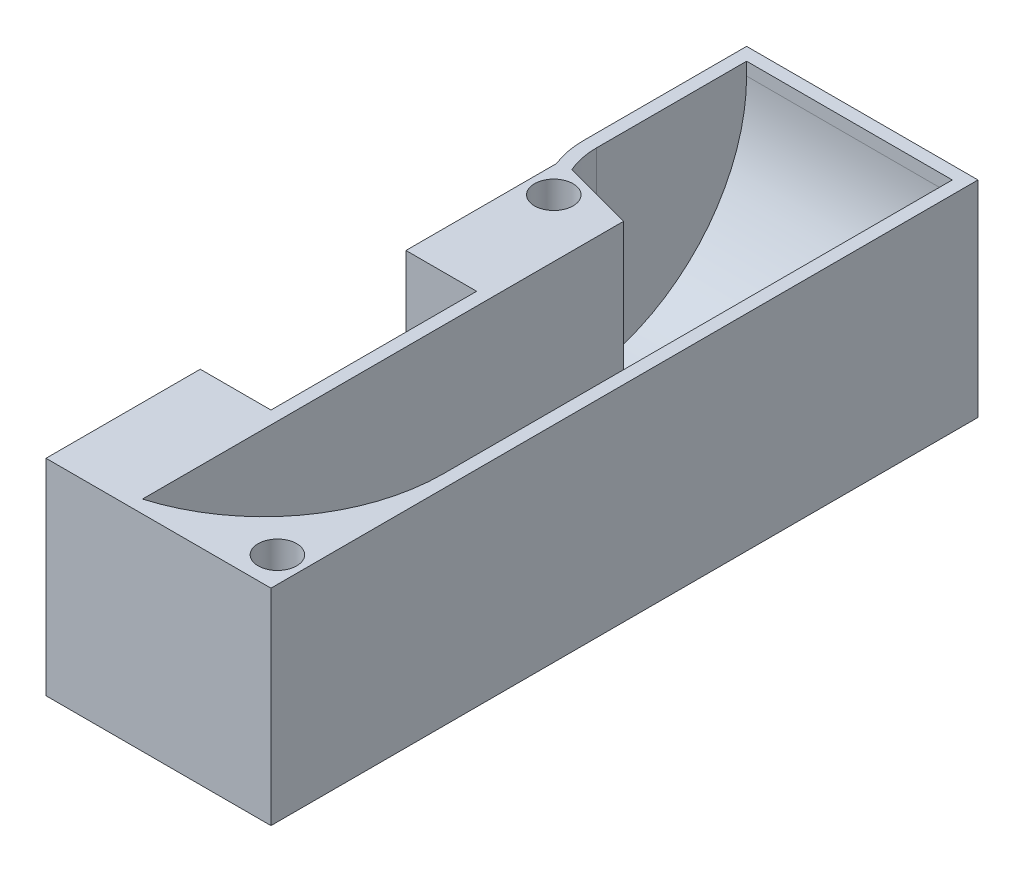
SolidWorks part; units mm, degrees
ref_plane "Front Plane" through (0, 0, 0) normal (0, 0, 1) x (1, 0, 0)
ref_plane "Top Plane" through (0, 0, 0) normal (0, 1, 0) x (1, 0, 0)
ref_plane "Right Plane" through (0, 0, 0) normal (1, 0, 0) x (0, 0, -1)
sketch "Sketch2" plane through (0, 0, 0) normal (0, -1, 0) x (1, 0, 0)
  line L0 (0, 0) -> (13, 0) construction
  line L18 (7.5, -8) -> (7.5, -19.7113)
  line L19 (7, -22.3094) -> (7, -35)
  line L20 (7, -35) -> (25, -35)
  line L21 (25, -35) -> (25, 20)
  line L22 (25, 20) -> (7.5, 20)
  line L23 (7.5, 20) -> (7.5, 8)
  line L24 (7.5, 8) -> (13, 8)
  line L25 (13, 8) -> (13, -8)
  line L26 (13, -8) -> (7.5, -8)
  arc A2 (7.5, -19.7113) -> (7, -22.3094) centre (14, -22.3094) ccw
  point P13 (0, 0)
  dimension "D8" = 7
  dimension "D1" = 13
  dimension "D2" = 16
  dimension "D3" = 5.5
  dimension "D4" = 20
  dimension "D5" = 17.5
  dimension "D6" = 55
  dimension "D7" = 7
  dimension "D9" = 12.6906
extrude "Boss-Extrude2" add sketch "Sketch2" along normal blind 16 separate body
shell "Shell1" thickness 1 removed face at (11.9876, 0, -7.1997)
fillet "Fillet1" radius 14 1 edges at (16, -15, -34)
sketch "Sketch3" plane through (0, 0, 0) normal (0, 1, 0) x (1, 0, 0)
  line L0 (14, 9) -> (8.5, 9)
  line L1 (8.5, 9) -> (8.5, 19.9115)
  line L2 (8.5, 19.9115) -> (14, 18.4378)
  line L3 (14, 18.4378) -> (14, 9)
  line L5 (14, -9) -> (8.5, -9)
  line L6 (14, -9) -> (14, -19)
  line L7 (14, -19) -> (8.5, -19)
  line L8 (8.5, -9) -> (8.5, -19)
  line L9 (11.25, -19) -> (11.25, -9) construction
  line L10 (14, -14) -> (8.5, -14) construction
  point P139 (11.25, -14)
  dimension "D1" = 75
extrude "Boss-Extrude3" add sketch "Sketch3" against normal up to next
sketch "Sketch4" plane through (7.5, 0, 0) normal (-1, 0, 0) x (0, 0, 1)
  line L0 (12.5, -13) -> (-12.5, -13) construction
  line L1 (0, 0) -> (0, -13) construction
  line L4 (8, -16) -> (-8, -16) construction
  circle A0 centre (-12.5, -13) radius 2
  circle A1 centre (12.5, -13) radius 2
  dimension "D1" = 4
  dimension "D2" = 25
  dimension "D3" = 3
extrude "Cut-Extrude1" cut sketch "Sketch4" against normal up to surface (6.5 mm away)
fillet "Fillet2" radius 14 1 edges at (24, -7.5, 19)
sketch "Sketch7" plane through (0, 0, 0) normal (0, 1, 0) x (1, 0, 0)
  line L0 (9.5, 17.5) -> (9.5, -17.5) construction
  line L1 (9.5, -17.5) -> (23, -17.5) construction
  line L2 (0, 0) -> (9.5, 0) construction
  circle A0 centre (23, -17.5) radius 1.5
  circle A1 centre (9.5, 17.5) radius 1.5
  dimension "D4" = 3
  dimension "D1" = 9.5
  dimension "D2" = 35
  dimension "D3" = 13.5
extrude "Cut-Extrude2" cut sketch "Sketch7" against normal blind 3
